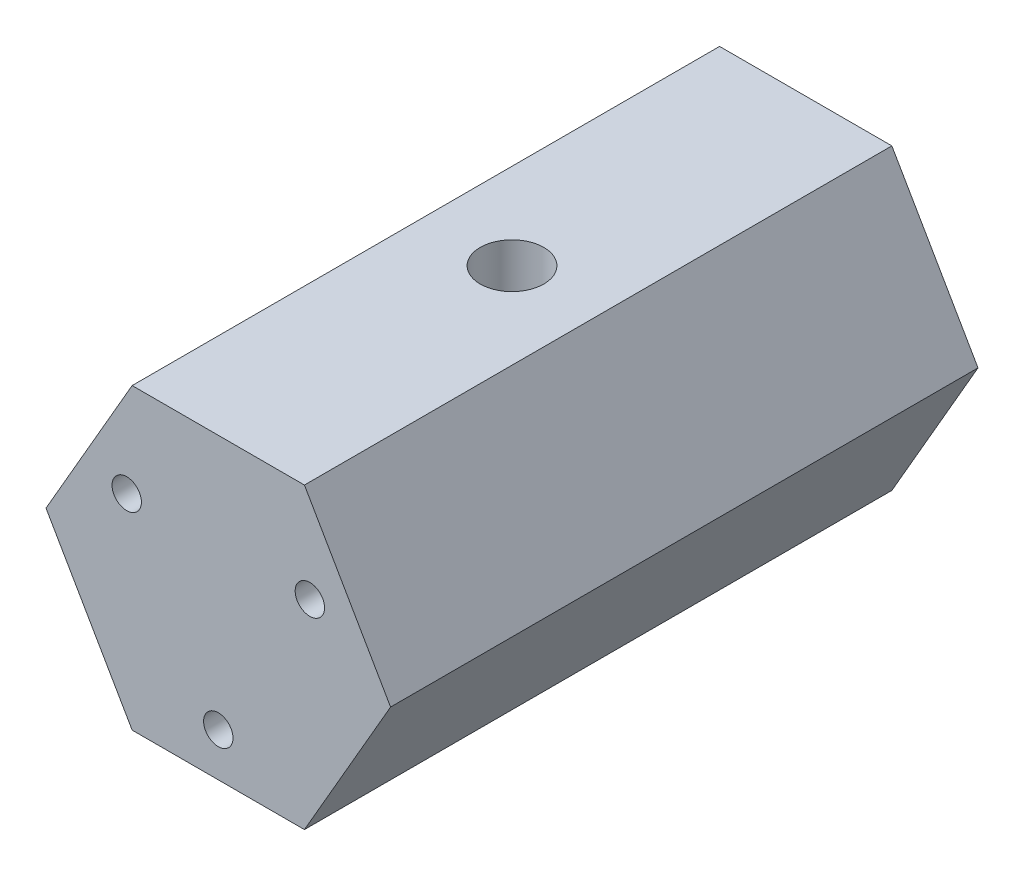
SolidWorks part; units mm, degrees
material "6061-T6 (SS)"
ref_plane "Front Plane" through (0, 0, 0) normal (0, 0, 1) x (1, 0, 0)
ref_plane "Top Plane" through (0, 0, 0) normal (0, 1, 0) x (1, 0, 0)
ref_plane "Right Plane" through (0, 0, 0) normal (1, 0, 0) x (0, 0, -1)
sketch "Sketch1" plane through (0, 0, 0) normal (0, 0, 1) x (1, 0, 0)
  line L7 (-7.3323, -12.7) -> (7.3323, -12.7)
  line L8 (7.3323, -12.7) -> (14.6647, 0)
  line L9 (14.6647, 0) -> (7.3323, 12.7)
  line L10 (7.3323, 12.7) -> (-7.3323, 12.7)
  line L11 (-7.3323, 12.7) -> (-14.6647, 0)
  line L12 (-14.6647, 0) -> (-7.3323, -12.7)
  circle A0 centre (0, 0) radius 9 construction
  circle A1 centre (-7.7942, 4.5) radius 1.25
  circle A2 centre (7.7942, 4.5) radius 1.25
  circle A3 centre (0, -9) radius 1.25
  circle A4 centre (0, 0) radius 12.7 construction
  circle A12 centre (0, 0) radius 9 construction
  point P6 (-16.1484, 0)
  point P11 (0, 0)
  point P12 (0, 0)
  point P13 (0, 0)
  point P14 (0, 0)
  point P15 (0, 0)
  point P16 (0, 0)
  point P23 (14.6647, 0)
  dimension "D1" = 3
  dimension "D2" = 2.5
  dimension "D3" = 25.4
extrude "Boss-Extrude1" add sketch "Sketch1" along normal blind 50
sketch "Sketch3" plane through (0, 12.7, 0) normal (0, 1, 0) x (1, 0, 0)
  line L0 (0, 0) -> (0, -50) construction
  line L1 (7.3323, -50) -> (-7.3323, -50) construction
  point P0 (0, -25)
hole_wizard "1/4-28 Tapped Hole1" positions "Sketch3" profile "Sketch4" tap size "1/4-28" standard "ANSI Inch" end condition through all
cosmetic thread "Hole Thread1" parameters "D2"=6.35
sketch "Sketch4" plane through (0, 12.7, 25) normal (1, 0, 0) x (0, 0, 1)
  line L0 (0, 0) -> (0, 25.4)
  line L1 (0, 25.4) -> (2.7051, 25.4)
  line L2 (2.7051, 25.4) -> (2.7051, 0)
  line L5 (2.7051, 0) -> (0, 0)
  line L11 (0, -6.35) -> (0, 107.95) construction
  dimension "Thru Tap Drill Dia." = 5.4102
  dimension "Thru Tap Drill Depth" = 25.4
equation "\"D1@Boss-Extrude1\"=\"Strut Length@Rocker Bogie Assy.Assembly\""
